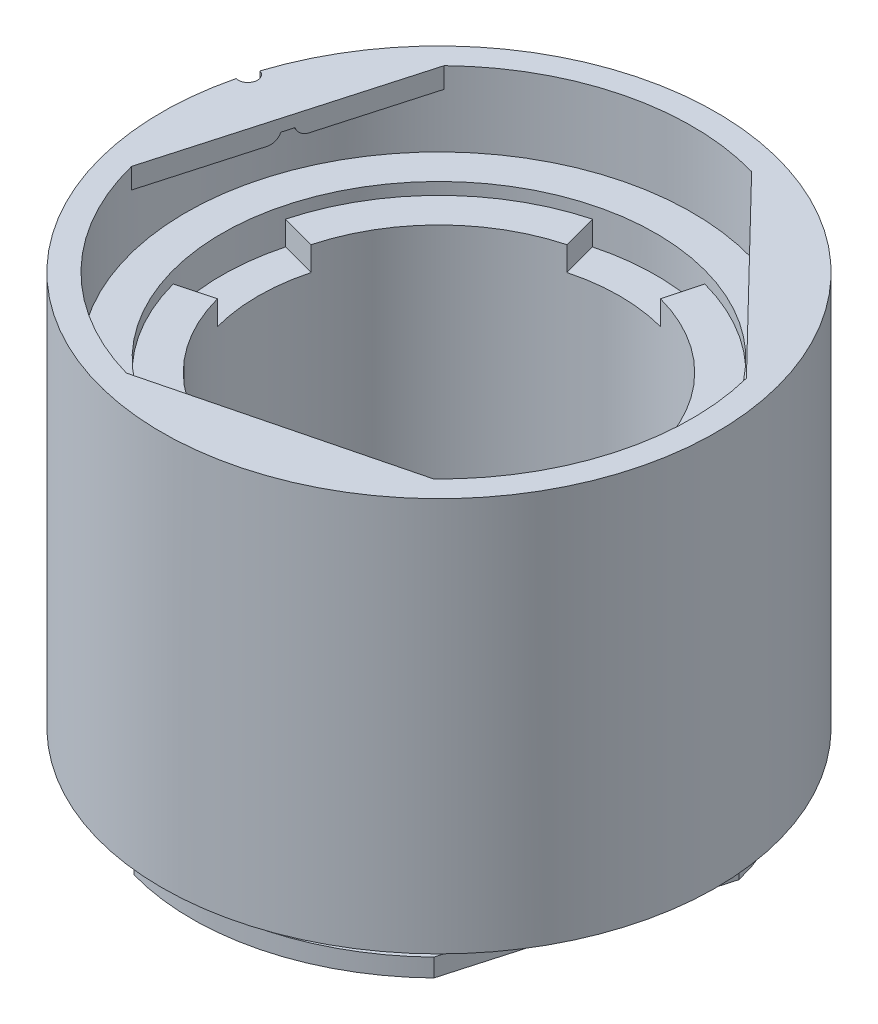
SolidWorks part; units mm, degrees
ref_plane "Front" through (0, 0, 0) normal (0, 0, 1) x (1, 0, 0)
ref_plane "Top" through (0, 0, 0) normal (0, 1, 0) x (1, 0, 0)
ref_plane "Right" through (0, 0, 0) normal (1, 0, 0) x (0, 0, -1)
sketch "Sketch1" plane through (0, 0, 0) normal (0, 1, 0) x (1, 0, 0)
  circle A0 centre (0, 0) radius 20.5
extrude "Boss-Extrude1" add sketch "Sketch1" along normal blind 1.5
sketch "Sketch2" plane through (0, 1.5, 0) normal (0, 1, 0) x (1, 0, 0)
  line L0 (-12.1923, 12.5538) -> (-12.889, 13.2712)
  line L1 (-16.9681, -4.2819) -> (-17.9377, -4.5266)
  line L2 (16.9681, 4.2819) -> (17.9377, 4.5266)
  line L3 (4.7758, 16.8357) -> (5.0487, 17.7978)
  line L4 (-4.7758, -16.8357) -> (-5.0487, -17.7978)
  line L5 (12.1923, -12.5538) -> (12.889, -13.2712)
  line L6 (-14.2824, 14.7059) -> (5.5945, 19.7219)
  line L7 (19.8769, 5.016) -> (14.2824, -14.7059)
  line L8 (-19.8769, -5.016) -> (-5.5945, -19.7219)
  line L9 (0, 0) -> (-14.2824, 14.7059) construction
  arc A0 (-19.8769, -5.016) -> (-5.5945, -19.7219) centre (0, 0) ccw
  arc A1 (-12.889, 13.2712) -> (-17.9377, -4.5266) centre (0, 0) ccw
  arc A2 (-12.1923, 12.5538) -> (-16.9681, -4.2819) centre (0, 0) ccw
  arc A3 (17.9377, 4.5266) -> (5.0487, 17.7978) centre (0, 0) ccw
  arc A4 (16.9681, 4.2819) -> (4.7758, 16.8357) centre (0, 0) ccw
  arc A5 (-5.0487, -17.7978) -> (12.889, -13.2712) centre (0, 0) ccw
  arc A6 (-4.7758, -16.8357) -> (12.1923, -12.5538) centre (0, 0) ccw
  arc A7 (14.2824, -14.7059) -> (19.8769, 5.016) centre (0, 0) ccw
  arc A8 (5.5945, 19.7219) -> (-14.2824, 14.7059) centre (0, 0) ccw
  point P13 (0, 0)
  dimension "D2" = 3
  dimension "D1" = 60
extrude "Cut-Extrude1" cut sketch "Sketch2" against normal blind 11
sketch "Sketch3" plane through (0, 1.5, 0) normal (0, 1, 0) x (1, 0, 0)
  circle A1 centre (0, 0) radius 17.5
extrude "Boss-Extrude2" add sketch "Sketch3" along normal blind 2
sketch "Sketch4" plane through (0, 3.5, 0) normal (0, 1, 0) x (1, 0, 0)
  circle A1 centre (0, 0) radius 23
extrude "Boss-Extrude3" add sketch "Sketch4" along normal blind 1
sketch "Sketch5" plane through (0, 4.5, 0) normal (0, 1, 0) x (1, 0, 0)
  circle A0 centre (0, 0) radius 23
  circle A1 centre (0, 0) radius 21
extrude "Boss-Extrude4" add sketch "Sketch5" along normal blind 30
sketch "Sketch6" plane through (0, 34.5, 0) normal (0, 1, 0) x (1, 0, 0)
  line L0 (0, 0) -> (-4.4043, 17.4529) construction
  line L2 (0, 0) -> (17.3168, -4.9122) construction
  line L5 (0, 0) -> (-12.9125, -12.5407) construction
  line L6 (14.6308, -15.0646) -> (-5.7309, -20.2029)
  line L7 (-20.3617, -5.1383) -> (-14.6308, 15.0646)
  line L8 (5.7309, 20.2029) -> (20.3617, 5.1383)
  circle A1 centre (0, 0) radius 23
  arc A4 (14.6308, -15.0646) -> (20.3617, 5.1383) centre (0, 0) ccw
  arc A5 (-20.3617, -5.1383) -> (-5.7309, -20.2029) centre (0, 0) ccw
  arc A6 (5.7309, 20.2029) -> (-14.6308, 15.0646) centre (0, 0) ccw
  point P14 (0, 0)
  point P18 (0, 0)
  point P22 (0, 0)
  dimension "D1" = 3
extrude "Boss-Extrude6" add sketch "Sketch6" along normal blind 1.7
sketch "Sketch7" plane through (0, 1.5, 0) normal (0, 1, 0) x (1, 0, 0)
  line L0 (0, 0) -> (4.2819, -16.9681) construction
  line L1 (4.0555, -18.05) -> (4.494, -20.0014)
  line L2 (4.9946, -17.813) -> (5.5346, -19.7388)
  arc A0 (-4.7758, -16.8357) -> (12.1923, -12.5538) centre (0, 0) ccw construction
  arc A1 (4.494, -20.0014) -> (5.5346, -19.7388) centre (0, 0) ccw
  arc A3 (4.0555, -18.05) -> (4.9946, -17.813) centre (0, 0) ccw
  dimension "D1" = 1.5
extrude "Boss-Extrude7" add sketch "Sketch7" along normal blind 0.8
fillet "Fillet3" radius 0.4 2 edges at (5.2646, 2.3, 18.7759) (4.2747, 2.3, 19.0257) first distance on face at (5.2646, 1.9, 18.7759) first distance on face at (4.2747, 1.9, 19.0257)
pattern_circular "CirPattern4" count 3 over 360 about axis through (0, 3.5, 0) along (0, 1, 0) of "Boss-Extrude7", "Fillet3"
ref_plane "Plane1" through (0, 34.2, 0) normal (0, 1, 0) x (1, 0, 0)
sketch "草图1" plane through (0, 36.2, 0) normal (0, 1, 0) x (1, 0, 0)
  line L0 (0, 0) -> (-12.5538, -12.1923) construction
  line L1 (0, 0) -> (-4.2819, 16.9681) construction
  line L2 (0, 0) -> (16.8357, -4.7758) construction
  circle A0 centre (0, 0) radius 18 construction
  circle A1 centre (0, 0) radius 17.5 construction
  circle A2 centre (0, 0) radius 18
  circle A3 centre (0, 0) radius 17
  point P9 (0, 0)
  dimension "D1" = 3
ref_plane "基准面1" through (0, 34.2, 0) normal (0, 1, 0) x (1, 0, 0)
sketch "草图9" plane through (0, 34.2, 0) normal (0, 1, 0) x (1, 0, 0)
  line L0 (0, 0) -> (5.016, -19.8769) construction
  line L3 (15.4424, 14.2314) -> (12.8687, 11.8595)
  line L4 (14.6764, 15.0201) -> (12.2303, 12.5167)
  arc A0 (4.494, -20.0014) -> (5.5346, -19.7388) centre (0, 0) ccw construction
  arc A5 (12.8687, 11.8595) -> (12.2303, 12.5167) centre (0, 0) ccw
  arc A6 (15.4424, 14.2314) -> (14.6764, 15.0201) centre (0, 0) ccw
  point P15 (0, 0)
extrude "切除-拉伸14" cut sketch "草图9" against normal blind 1 and the other way blind 1
fillet "圆角4" radius 1 2 edges at (14.4102, 34.5, -13.2802) (13.6954, 34.5, -14.0162)
pattern_circular "阵列(圆周)2" count 3 over 360 about axis through (0, 36.2, 0) along (0, 1, 0) of "切除-拉伸14", "圆角4"
sketch "草图15" plane through (0, 4.5, 0) normal (0, 1, 0) x (1, 0, 0)
  line L0 (0, 0) -> (-4.2819, 16.9681) construction
  circle A0 centre (0, 0) radius 21
  circle A5 centre (0, 0) radius 15
extrude "凸台-拉伸6" add sketch "草图15" along normal blind 24.5
sketch "草图17" plane through (0, 4.5, 0) normal (0, 1, 0) x (1, 0, 0)
  circle A0 centre (0, 0) radius 15
extrude "切除-拉伸17" cut sketch "草图17" against normal blind 32
sketch "草图20" plane through (0, 29, 0) normal (0, 1, 0) x (1, 0, 0)
  circle A0 centre (0, 0) radius 21
  circle A1 centre (0, 0) radius 18
extrude "凸台-拉伸8" add sketch "草图20" along normal blind 1
sketch "草图24" plane through (0, 36.2, 0) normal (0, 1, 0) x (1, 0, 0)
  line L0 (0, 0) -> (-17.4962, 4.9631) construction
  circle A0 centre (-22.127, 6.2767) radius 0.8
  circle A1 centre (0, 0) radius 23 construction
extrude "切除-拉伸20" cut sketch "草图24" against normal blind 18
sketch "草图25" plane through (0, 29, 0) normal (0, 1, 0) x (1, 0, 0)
  line L0 (0, 0) -> (0, 13) construction
  line L1 (-3.8823, 14.4889) -> (-4.6587, 17.3867)
  line L2 (3.8823, 14.4889) -> (4.6587, 17.3867)
  arc A0 (4.6587, 17.3867) -> (-4.6587, 17.3867) centre (0, 0) ccw
  arc A1 (3.8823, 14.4889) -> (-3.8823, 14.4889) centre (0, 0) ccw
  dimension "D1" = 15
extrude "切除-拉伸21" cut sketch "草图25" against normal blind 2
pattern_circular "阵列(圆周)3" count 4 over 360 about axis through (0, 36.2, 0) along (0, 1, 0) of "切除-拉伸21"
